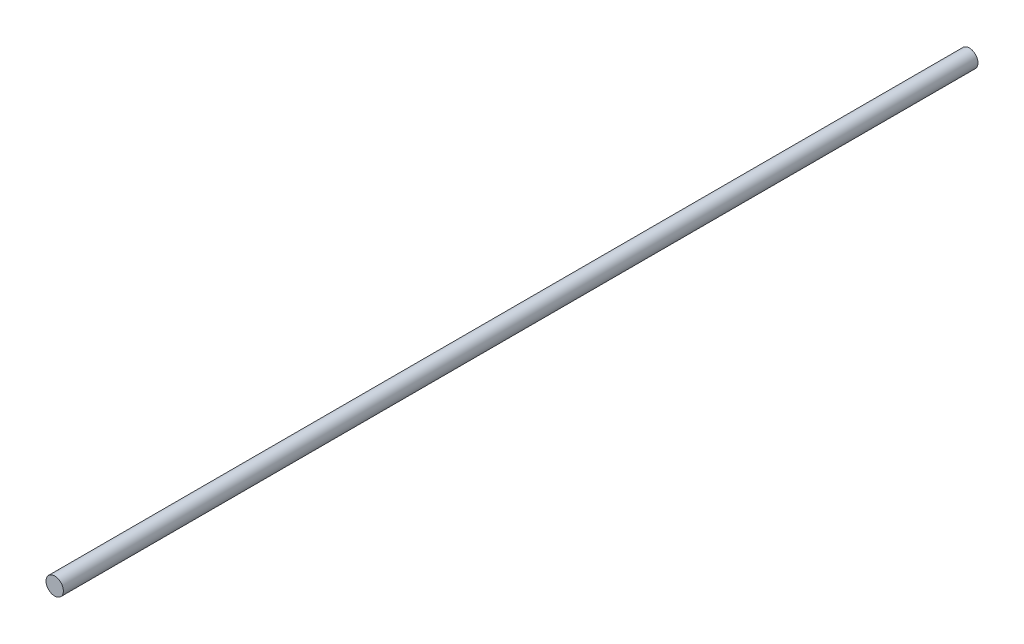
SolidWorks part; units mm, degrees
material "AISI 316 Stainless Steel Sheet (SS)"
ref_plane "Front (1)" through (0, 0, 0) normal (0, 0, 1) x (1, 0, 0)
ref_plane "Top (2)" through (0, 0, 0) normal (0, 1, 0) x (1, 0, 0)
ref_plane "Right (3)" through (0, 0, 0) normal (1, 0, 0) x (0, 0, -1)
ref_axis "X Axis" through (13.5064, 0, 0) along (-1, 0, 0)
ref_axis "Y Axis" through (0, 12.3593, 0) along (0, -1, 0)
ref_axis "Z Axis" through (0, 0, 14.1119) along (0, 0, -1)
sketch "Sketch2" plane through (0, 0, 0) normal (1, 0, 0) x (0, 0, -1)
  line L0 (-19.1, 0) -> (0, 0) construction
  line L1 (-19.1, 0) -> (401.3, 0)
  line L2 (-19.1, 0) -> (-19.1, 4)
  line L3 (-19.1, 4) -> (401.3, 4)
  line L4 (401.3, 0) -> (401.3, 4)
  line L5 (-16.1, 4) -> (-16.1, -4) construction
  line L6 (398.3, -4) -> (398.3, 4) construction
  dimension "D1" = 8
  dimension "D2" = 420.4
  dimension "D3" = 3
  dimension "D4" = 3
revolve "Revolve1" add sketch "Sketch2" angle 360 about L0
cosmetic thread "Cosmetic Thread2"
